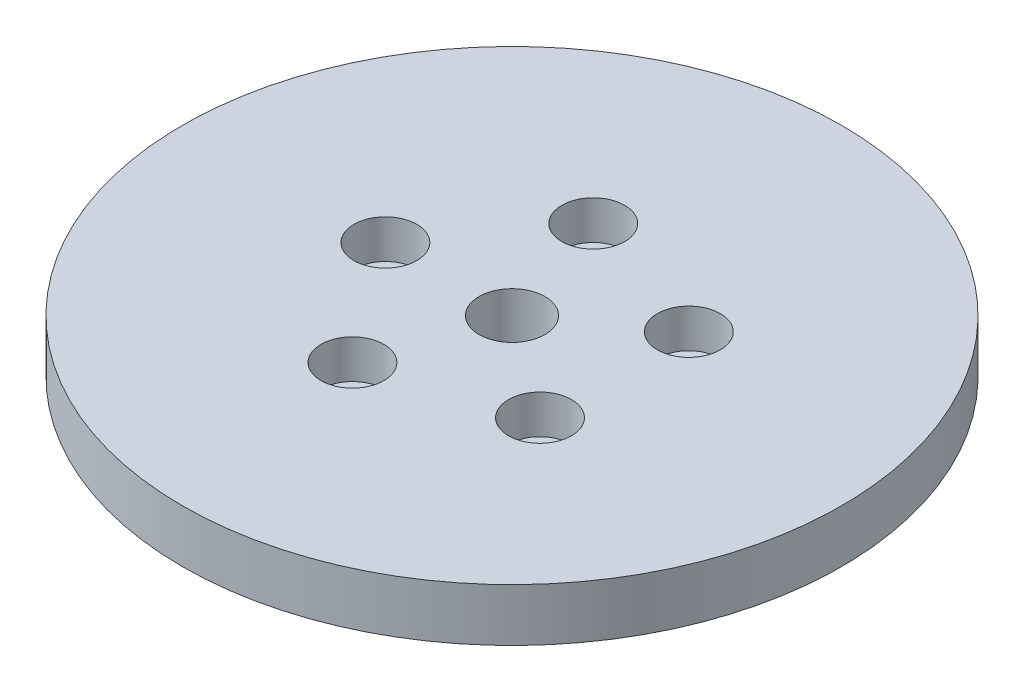
SolidWorks part; units mm, degrees
ref_plane "Front Plane" through (0, 0, 0) normal (0, 0, 1) x (1, 0, 0)
ref_plane "Top Plane" through (0, 0, 0) normal (0, 1, 0) x (1, 0, 0)
ref_plane "Right Plane" through (0, 0, 0) normal (1, 0, 0) x (0, 0, -1)
sketch "Sketch1" plane through (0, 0, 0) normal (0, 1, 0) x (1, 0, 0)
  circle A0 centre (0, 0) radius 75
  dimension "FLANGE_OD" = 150
extrude "Boss-Extrude1" add sketch "Sketch1" along normal blind 12
sketch "Sketch2" plane through (0, 0, 0) normal (0, 1, 0) x (1, 0, 0)
  circle A0 centre (0, 0) radius 7.5
  dimension "BORE_D" = 15
extrude "Cut-Extrude1" cut sketch "Sketch2" along normal through all
sketch "Sketch3" plane through (0, 12, 0) normal (0, 1, 0) x (1, 0, 0)
  circle A0 centre (0, 0) radius 28.8136 construction
  circle A1 centre (-28.8136, 0) radius 7.1558
  dimension "BOLT_D" = 14.3116
  dimension "BOLT_PCD" = 57.6272
extrude "Cut-Extrude2" cut sketch "Sketch3" against normal blind 8.8144
pattern_circular "CirPattern1" count 5 over 360 about axis through (0, 0, 0) along (0, 1, 0) of "Cut-Extrude2"
